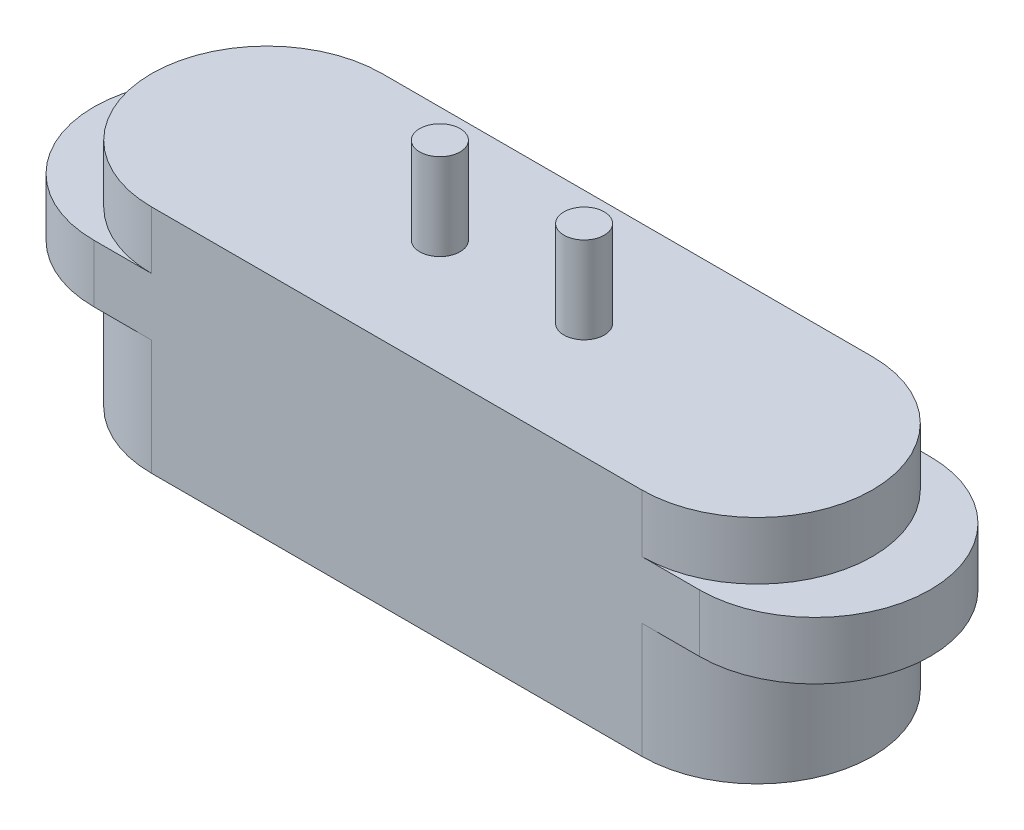
SolidWorks part; units mm, degrees
ref_plane "Front Plane" through (0, 0, 0) normal (0, 0, 1) x (1, 0, 0)
ref_plane "Top Plane" through (0, 0, 0) normal (0, 1, 0) x (1, 0, 0)
ref_plane "Right Plane" through (0, 0, 0) normal (1, 0, 0) x (0, 0, -1)
sketch "Sketch1" plane through (0, 0, 0) normal (0, 1, 0) x (1, 0, 0)
  line L0 (-5.25, 0) -> (5.25, 0) construction
  line L1 (-5.25, 2) -> (5.25, 2)
  line L2 (-5.25, -2) -> (5.25, -2)
  line L3 (-7.25, 0) -> (-7.25, 3.2735) construction
  line L4 (-4.25, 0) -> (4.25, 0) construction
  line L5 (7.25, 0) -> (7.25, 3.2735) construction
  line L6 (-4.25, 2) -> (4.25, 2)
  line L7 (-4.25, -2) -> (4.25, -2)
  line L8 (-6.25, 0) -> (-6.25, -6.6568) construction
  line L10 (6.25, 0) -> (6.25, -6.0417) construction
  arc A0 (-5.25, 2) -> (-5.25, -2) centre (-5.25, 0) ccw
  arc A1 (5.25, -2) -> (5.25, 2) centre (5.25, 0) ccw
  arc A2 (-4.25, 2) -> (-4.25, -2) centre (-4.25, 0) ccw
  arc A3 (4.25, -2) -> (4.25, 2) centre (4.25, 0) ccw
  point P2 (0, 0)
  point P14 (0, 0)
  dimension "D1" = 14.5
  dimension "D2" = 4
  dimension "D3" = 4
  dimension "D4" = 12.5
extrude "Boss-Extrude1" add sketch "Sketch1" along normal blind 4 contours L2 A3 L1 A2 region at (0, 0, 0)
extrude "Boss-Extrude2" add sketch "Sketch1<3>" along normal blind 1 from offset 2 contours A3 L2 A1 L1 | A2 L1 A0 L2 region at (-6.3208, 0, 0) region at (6.3208, 0, 0)
sketch "Sketch1<3>" plane through (0, 0, 0) normal (0, 1, 0) x (1, 0, 0) same geometry as "Sketch1"
sketch "Sketch2" plane through (0, 4, 0) normal (0, 1, 0) x (1, 0, 0)
  line L0 (-1.25, 0) -> (1.25, 0) construction
  circle A0 centre (-1.25, 0) radius 0.35
  circle A1 centre (1.25, 0) radius 0.35
  point P4 (0, 0)
  dimension "D1" = 0.7
  dimension "D2" = 2.5
extrude "Boss-Extrude3" add sketch "Sketch2" along normal blind 1.5
sketch "Sketch3" plane through (0, 0, 0) normal (0, -1, 0) x (1, 0, 0)
  circle A0 centre (1.25, 0) radius 0.35 construction
  circle A1 centre (-1.25, 0) radius 0.35 construction
  circle A2 centre (1.25, 0) radius 0.35 construction
  circle A3 centre (-1.25, 0) radius 0.35 construction
  circle A4 centre (-1.25, 0) radius 0.75
  circle A5 centre (1.25, 0) radius 0.75
  circle A6 centre (-4.25, 0) radius 1.25
  circle A7 centre (4.25, 0) radius 1.25
  dimension "D1" = 1.5
  dimension "D2" = 2.5
extrude "Cut-Extrude1" cut sketch "Sketch3" against normal blind 0.01 contours A4 | A5 | A7 | A6 region at (-1.25, 0, 0) region at (1.25, 0, 0) region at (4.25, 0, 0)
